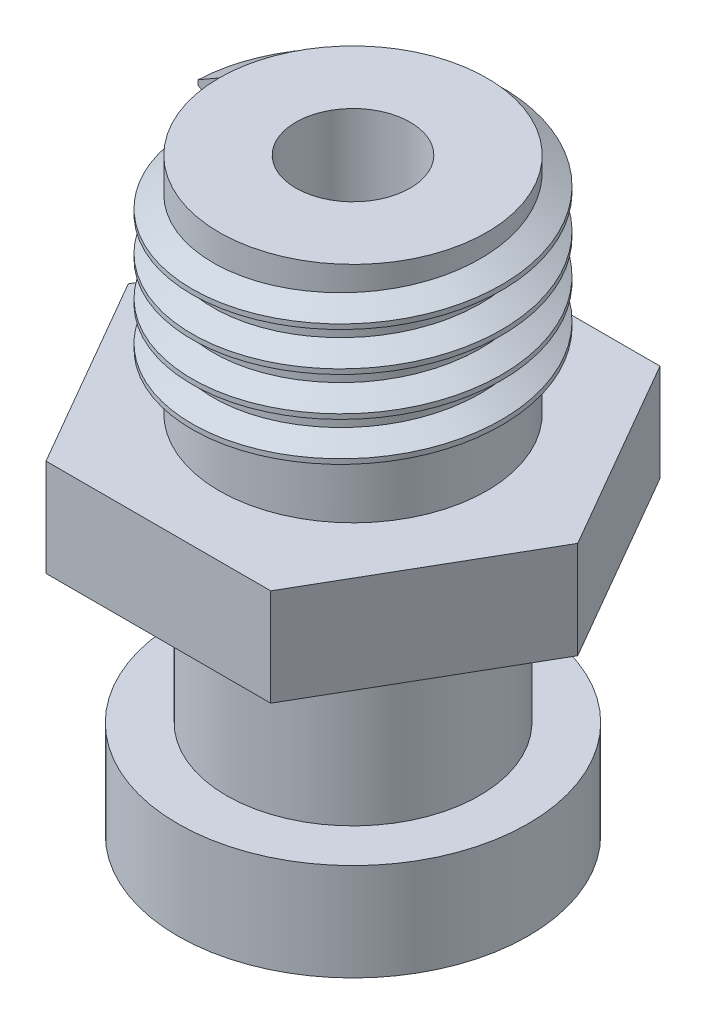
SolidWorks part; units mm, degrees
ref_plane "Plan de face" through (0, 0, 0) normal (0, 0, 1) x (1, 0, 0)
ref_plane "Plan de dessus" through (0, 0, 0) normal (0, 1, 0) x (1, 0, 0)
ref_plane "Plan de droite" through (0, 0, 0) normal (1, 0, 0) x (0, 0, -1)
sketch "Esquisse1" plane through (0, 0, 0) normal (1, 0, 0) x (0, 0, -1)
  line L1 (0, 0) -> (-3.6, 0)
  line L2 (-3.6, 0) -> (-3.6, 2)
  line L3 (-3.6, 2) -> (-2.6, 2)
  line L4 (-2.6, 2) -> (-2.6, 5.5)
  line L8 (0, 0) -> (0, 5.5)
  line L10 (-2.6, 5.5) -> (0, 5.5)
  dimension "D1" = 3.5
  dimension "D2" = 2
  dimension "D3" = 2.6
  dimension "D4" = 3.6
revolve "Révolution1" add sketch "Esquisse1" angle 360 about L8
sketch "Esquisse3" plane through (0, 5.5, 0) normal (0, 1, 0) x (1, 0, 0)
  line L1 (2.3094, -4) -> (4.6188, 0)
  line L2 (4.6188, 0) -> (2.3094, 4)
  line L3 (2.3094, 4) -> (-2.3094, 4)
  line L4 (-2.3094, 4) -> (-4.6188, 0)
  line L5 (-4.6188, 0) -> (-2.3094, -4)
  line L6 (-2.3094, -4) -> (2.3094, -4)
  circle A0 centre (0, 0) radius 4 construction
  dimension "D1" = 8
extrude "Boss.-Extru.1" add sketch "Esquisse3" along normal blind 2
sketch "Esquisse4" plane through (0, 7.5, 0) normal (0, 1, 0) x (1, 0, 0)
  circle A0 centre (0, 0) radius 2.75
  dimension "D1" = 5.5
extrude "Boss.-Extru.2" add sketch "Esquisse4" along normal blind 4.6
thread "Filetage1" pitch 0.8 method extrude profile "Profil de filetage1" start angle 0, offset 0, length 0, pitch 0.8, diameter 5.5
ref_plane "Plan1" through (-2.75, 12.1, 0) normal (0, 0, 1) x (-1, 0, 0)
sketch "Profil de filetage1" plane through (-2.75, 12.1, 0) normal (0, 0, 1) x (-1, 0, 0)
  line L0 (0, 0) -> (0, 0.8) construction
  line L1 (0, 0) -> (0.433, 0.25)
  line L2 (0.433, 0.25) -> (0.433, 0.35)
  line L3 (0.433, 0.35) -> (0, 0.6)
  line L4 (0.433, 0.3) -> (0, 0.3) construction
  line L11 (0, 0) -> (0, 0.6)
  point P2 (0, 0)
  dimension "Pitch" = 0.8
  dimension "Profile_Angle" = 60
  dimension "Profile_Land" = 0.1
  dimension "Profile_Height" = 0.433
sketch "Esquisse9" plane through (0, 12.1, 0) normal (0, 1, 0) x (1, 0, 0)
  circle A0 centre (0, 0) radius 1.175
  dimension "D1" = 2.35
extrude "Enlèv. mat.-Extru.4" cut sketch "Esquisse9" against normal through all
